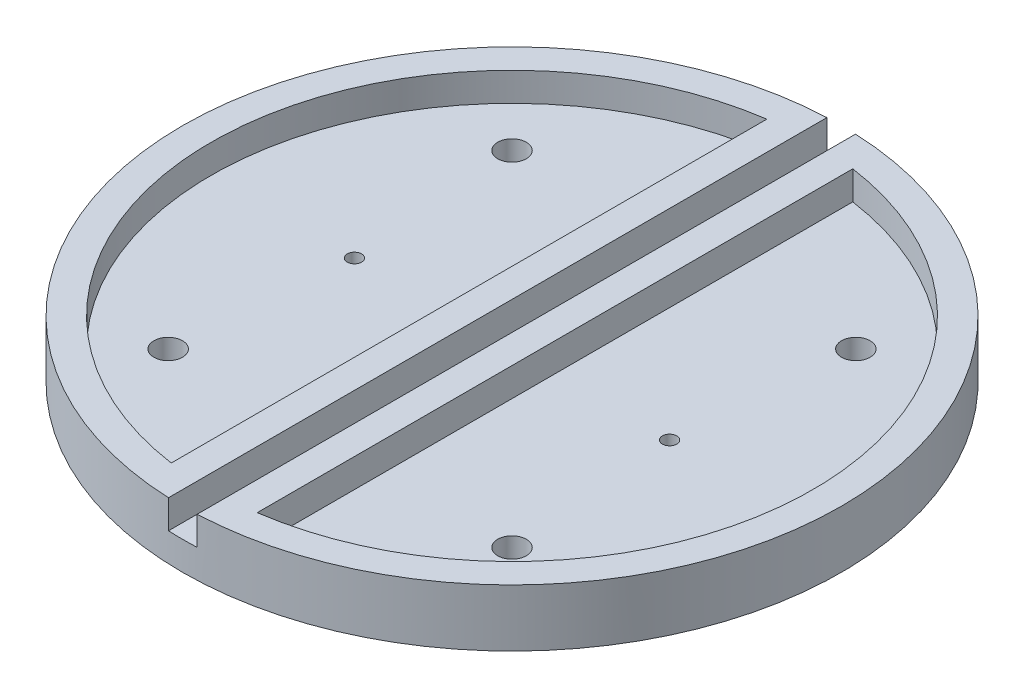
SolidWorks part; units mm, degrees
material "ABS"
ref_plane "Front Plane" through (0, 0, 0) normal (0, 0, 1) x (1, 0, 0)
ref_plane "Top Plane" through (0, 0, 0) normal (0, 1, 0) x (1, 0, 0)
ref_plane "Right Plane" through (0, 0, 0) normal (1, 0, 0) x (0, 0, -1)
sketch "Sketch5" plane through (0, 0, 0) normal (0, 1, 0) x (1, 0, 0)
  circle A0 centre (0, 0) radius 73.025
  circle A1 centre (38.1, 38.1) radius 3.175
  circle A2 centre (38.1, -38.1) radius 3.175
  circle A3 centre (-38.1, 38.1) radius 3.175
  circle A4 centre (-38.1, -38.1) radius 3.175
extrude "PlateBase" add sketch "Sketch5" along normal blind 6.35
sketch "Sketch6" plane through (0, 6.35, 0) normal (0, 1, 0) x (1, 0, 0)
  line L1 (3.175, 0) -> (3.175, 72.9559)
  line L3 (3.175, 0) -> (3.175, -72.9559)
  line L4 (0, 0) -> (3.175, 0)
  line L5 (-3.175, 0) -> (-3.175, 72.9559)
  line L6 (-9.525, 0) -> (-9.525, 72.4011)
  line L7 (-9.525, 0) -> (-9.525, -72.4011)
  line L8 (-3.175, 0) -> (-3.175, -72.9559)
  line L9 (9.525, 0) -> (9.525, 72.4011)
  line L10 (9.525, 0) -> (9.525, -72.4011)
  circle A0 centre (0, 0) radius 73.025 construction
  circle M4 centre (0, 0) radius 73.025
extrude "PlateTop" add sketch "Sketch6" along normal blind 6.35 contours L8 L5 L6 L7 M4 | L10 L9 L1 L3 M4 region at (6.346, 6.35, 0) region at (-6.346, 6.35, 0)
sketch "Sketch9" plane through (0, 6.35, 0) normal (0, 1, 0) x (1, 0, 0)
  circle A0 centre (0, 0) radius 66.675
  circle A1 centre (0, 0) radius 73.025
extrude "PlateWalls" add sketch "Sketch9" along normal blind 6.35
sketch "Sketch11" plane through (0, 12.7, 0) normal (0, 1, 0) x (1, 0, 0)
  line L0 (-3.175, 66.5994) -> (-3.175, 72.9559)
  line L1 (3.175, 66.5994) -> (3.175, 72.9559)
  line L2 (-3.175, 66.5994) -> (3.175, 66.5994)
  circle A0 centre (0, 0) radius 73.025 construction
  arc A1 (-3.175, 72.9559) -> (3.175, 72.9559) centre (0, 0) cw
extrude "TopSlotCut" cut sketch "Sketch11" against normal blind 6.35
sketch "Sketch12" plane through (0, 12.7, 0) normal (0, 1, 0) x (1, 0, 0)
  line L0 (-3.175, -66.5994) -> (-3.175, -72.9559)
  line L1 (3.175, -66.5994) -> (3.175, -72.9559)
  line L2 (-3.175, -66.5994) -> (3.175, -66.5994)
  arc A0 (-3.175, 72.9559) -> (3.175, 72.9559) centre (0, 0) ccw construction
  arc A1 (3.175, -72.9559) -> (-3.175, -72.9559) centre (0, 0) cw
extrude "BottomSlotCut" cut sketch "Sketch12" against normal blind 6.35
sketch "Sketch13" plane through (0, 6.35, 0) normal (0, 1, 0) x (1, 0, 0)
  circle A0 centre (34.925, 0) radius 1.5875
extrude "RightThruHole" cut sketch "Sketch13" against normal blind 6.35
sketch "Sketch14" plane through (0, 6.35, 0) normal (0, 1, 0) x (1, 0, 0)
  circle A0 centre (-34.925, 0) radius 1.5875
extrude "LeftThruHole" cut sketch "Sketch14" against normal blind 6.35
